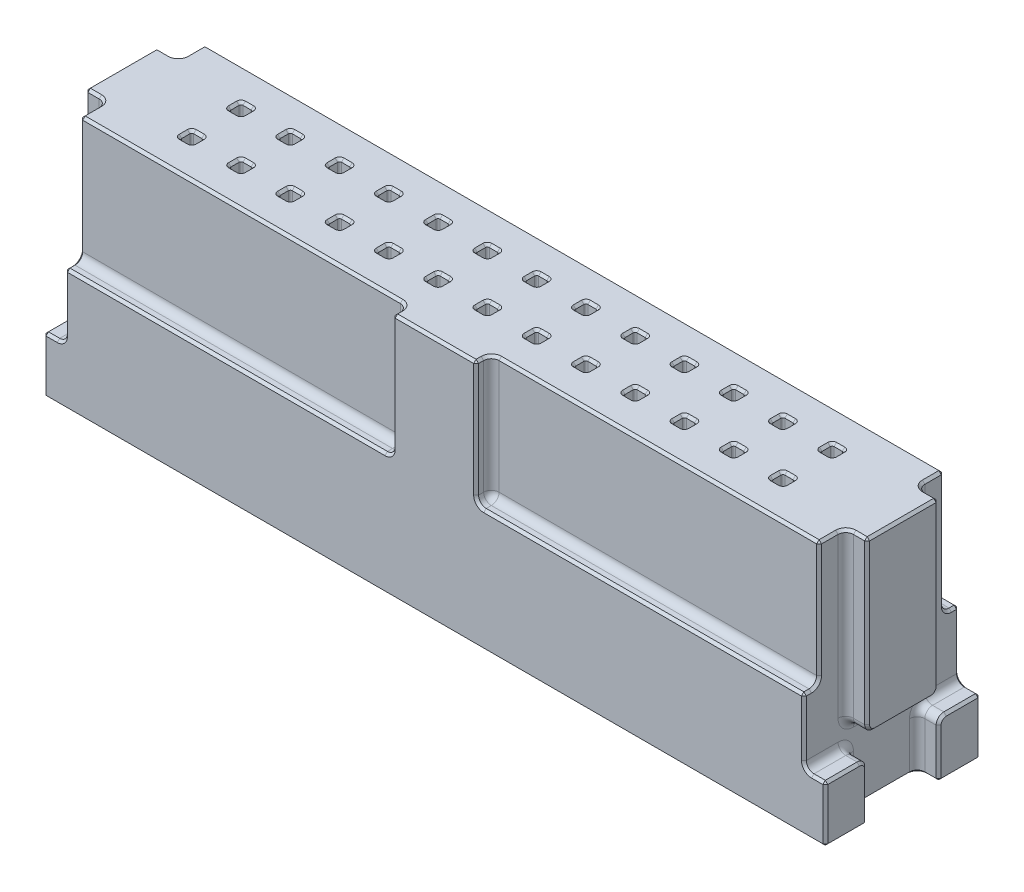
SolidWorks part; units mm, degrees
ref_plane "Front Plane" through (0, 0, 0) normal (0, 0, 1) x (1, 0, 0)
ref_plane "Top Plane" through (0, 0, 0) normal (0, 1, 0) x (1, 0, 0)
ref_plane "Right Plane" through (0, 0, 0) normal (1, 0, 0) x (0, 0, -1)
sketch "Sketch1" plane through (0, 0, 0) normal (0, 1, 0) x (1, 0, 0)
  line L1 (-20.1549, -4.0005) -> (20.1549, -4.0005)
  line L2 (-20.1549, -4.0005) -> (-20.1549, 4.0005)
  line L3 (-20.1549, 4.0005) -> (20.1549, 4.0005)
  line L4 (20.1549, -4.0005) -> (20.1549, 4.0005)
  line L5 (-20.1549, -4.0005) -> (20.1549, 4.0005) construction
  line L6 (-20.1549, 4.0005) -> (20.1549, -4.0005) construction
  point P0 (0, 0)
  dimension "D1" = 40.3098
  dimension "D2" = 8.001
extrude "Boss-Extrude1" add sketch "Sketch1" along normal blind 12.7 contours L3 L4 L1 L2
sketch "Sketch2" plane through (0, 12.7, 0) normal (0, 1, 0) x (1, 0, 0)
  line L1 (-20.1549, 4.0005) -> (-19.05, 4.0005)
  line L2 (-20.1549, 4.0005) -> (-20.1549, 1.8415)
  line L3 (-20.1549, 1.8415) -> (-19.05, 1.8415)
  line L4 (-19.05, 4.0005) -> (-19.05, 1.8415)
  line L5 (-20.1549, -4.0005) -> (-19.05, -4.0005)
  line L6 (-20.1549, -4.0005) -> (-20.1549, -1.8415)
  line L7 (-20.1549, -1.8415) -> (-19.05, -1.8415)
  line L8 (-19.05, -4.0005) -> (-19.05, -1.8415)
  line L9 (20.1549, 4.0005) -> (19.05, 4.0005)
  line L10 (20.1549, 4.0005) -> (20.1549, 1.8415)
  line L11 (20.1549, 1.8415) -> (19.05, 1.8415)
  line L12 (19.05, 4.0005) -> (19.05, 1.8415)
  line L13 (20.1549, -4.0005) -> (19.05, -4.0005)
  line L14 (20.1549, -4.0005) -> (20.1549, -1.8415)
  line L15 (20.1549, -1.8415) -> (19.05, -1.8415)
  line L16 (19.05, -4.0005) -> (19.05, -1.8415)
  dimension "D1" = 1.1049
  dimension "D2" = 2.159
extrude "Cut-Extrude1" cut sketch "Sketch2" against normal blind 9.7993
sketch "Sketch4" plane through (0, 12.7, 0) normal (0, 1, 0) x (1, 0, 0)
  line L1 (-20.1549, -1.8415) -> (-19.05, -1.8415)
  line L2 (-20.1549, -1.8415) -> (-20.1549, 1.8415)
  line L3 (-20.1549, 1.8415) -> (-19.05, 1.8415)
  line L4 (-19.05, -1.8415) -> (-19.05, 1.8415)
  line L5 (20.1549, -1.8415) -> (19.05, -1.8415)
  line L6 (20.1549, -1.8415) -> (20.1549, 1.8415)
  line L7 (20.1549, 1.8415) -> (19.05, 1.8415)
  line L8 (19.05, -1.8415) -> (19.05, 1.8415)
extrude "Cut-Extrude2" cut sketch "Sketch4" against normal up to next from offset 8.7312 offset against normal yes
sketch "Sketch5" plane through (0, 12.7, 0) normal (0, 1, 0) x (1, 0, 0)
  line L0 (19.05, -1.8415) -> (19.05, -4.0005) construction
  line L1 (-19.05, -4.0005) -> (-2.1501, -4.0005)
  line L2 (-19.05, -4.0005) -> (-19.05, -3.2144)
  line L3 (-19.05, -3.2144) -> (-2.1501, -3.2144)
  line L4 (19.05, -4.0005) -> (19.05, -3.2144)
  line L5 (19.05, 4.0005) -> (19.05, 1.8415) construction
  line L6 (-19.05, 4.0005) -> (19.05, 4.0005)
  line L7 (-19.05, 4.0005) -> (-19.05, 3.2144)
  line L8 (-19.05, 3.2144) -> (19.05, 3.2144)
  line L9 (19.05, 4.0005) -> (19.05, 3.2144)
  line L10 (0, -3.2144) -> (0, 3.2144) construction
  line L11 (-2.1501, -3.2144) -> (-2.1501, -4.0005)
  line L12 (2.1501, -3.2144) -> (2.1501, -4.0005)
  line L13 (2.1501, -3.6074) -> (-2.1501, -3.6074) construction
  line L14 (0, -3.6074) -> (0, -3.2144) construction
  line L15 (2.1501, -3.2144) -> (19.05, -3.2144)
  line L16 (2.1501, -4.0005) -> (19.05, -4.0005)
  dimension "D1" = 6.4287
  dimension "D2" = 4.3002
extrude "Cut-Extrude3" cut sketch "Sketch5" against normal blind 6.4008 contours L8 L9 L6 L7
sketch "Sketch6" plane through (0, 12.7, 0) normal (0, 1, 0) x (1, 0, 0)
  line L0 (-20.1549, -1.8415) -> (-20.1549, 1.8415) construction
  line L1 (-15.5499, 0.9601) -> (-14.9301, 0.9601)
  line L2 (-15.5499, 0.9601) -> (-15.5499, 1.5799)
  line L3 (-15.5499, 1.5799) -> (-14.9301, 1.5799)
  line L4 (-14.9301, 0.9601) -> (-14.9301, 1.5799)
  line L5 (-15.5499, 0.9601) -> (-14.9301, 1.5799) construction
  line L6 (-15.5499, 1.5799) -> (-14.9301, 0.9601) construction
  line L7 (19.05, 4.0005) -> (-19.05, 4.0005) construction
  point P0 (-15.24, 1.27)
  dimension "D1" = 0.6198
  dimension "D2" = 4.605
  dimension "D3" = 2.4206
extrude "Cut-Extrude4" cut sketch "Sketch6" against normal blind 6.1011 contours L1 L4 L3 L2
pattern_linear "LPattern1" count 13 spacing 2.54 along (1, 0, 0) count 2 spacing 2.54 along (0, 0, 1) of "Cut-Extrude4"
fillet "Fillet1" radius 0.3969 29 edges at (19.05, 8.3344, -1.8415) (19.05, 8.3344, 1.8415) (-19.05, 8.3344, 1.8415) (-19.05, 8.3344, -1.8415) (0, 6.2992, -3.2144) (-10.6001, 6.2992, 3.2144) (-2.1501, 6.2992, 3.6074) (-2.1501, 9.4996, 3.2144) (2.1501, 6.2992, 3.6074) (10.6001, 6.2992, 3.2144) (2.1501, 9.4996, 3.2144) (-19.05, 3.9688, 0) (19.05, 3.9688, 0) (-19.6025, 3.9688, 1.8415) (-19.6025, 3.9688, -1.8415) (-19.6025, 2.9007, -1.8415) (-19.6025, 2.9007, 1.8415) (19.6024, 3.9688, 1.8415) (19.6024, 3.9688, -1.8415) (19.6024, 2.9007, 1.8415) (19.6024, 2.9007, -1.8415) (19.05, 1.4503, -1.8415) (19.05, 2.9007, -2.921) (19.05, 1.4503, 1.8415) (19.05, 2.9007, 2.921) (-19.05, 2.9007, 2.921) (-19.05, 1.4503, 1.8415) (-19.05, 1.4503, -1.8415) (-19.05, 2.9007, -2.921)
fillet "Fillet3" radius 0.0992 44 edges at (14.9301, 9.6495, 0.9601) (13.0099, 9.6495, 0.9601) (7.3101, 9.6495, 0.9601) (5.3899, 9.6495, 1.5799) (2.8499, 9.6495, 0.9601) (0.3099, 9.6495, 1.5799) (0.3099, 9.6495, 0.9601) (-2.2301, 9.6495, 1.5799) (-2.2301, 9.6495, 0.9601) (-5.3899, 9.6495, 1.5799) (-5.3899, 9.6495, 0.9601) (-10.4699, 9.6495, 1.5799) (-13.0099, 9.6495, 1.5799) (10.4699, 9.6495, -0.9601) (10.4699, 9.6495, -1.5799) (9.8501, 9.6495, -1.5799) (7.3101, 9.6495, -1.5799) (0.3099, 9.6495, -0.9601) (-2.8499, 9.6495, -1.5799) (-4.7701, 9.6495, -0.9601) (-7.9299, 9.6495, -0.9601) (-9.8501, 9.6495, -0.9601) (-9.8501, 9.6495, -1.5799) (-13.0099, 9.6495, -0.9601) (-12.3901, 9.6495, -0.9601) (5.08, 6.5989, -1.5799) (5.08, 6.5989, -0.9601) (7.62, 6.5989, -1.5799) (-10.16, 6.5989, 1.5799) (0.3099, 6.5989, 1.27) (0, 6.5989, 1.5799) (2.54, 6.5989, 0.9601) (2.8499, 6.5989, 1.27) (5.08, 6.5989, 1.5799) (7.3101, 6.5989, 1.27) (7.62, 6.5989, 0.9601) (13.0099, 6.5989, 1.27) (-2.2301, 6.5989, -1.27) (-4.7701, 6.5989, -1.27) (-5.08, 6.5989, -1.5799) (-7.62, 6.5989, -1.5799) (-10.16, 6.5989, -0.9601) (-9.8501, 6.5989, -1.27) (-12.3901, 6.5989, -1.27)
chamfer "Chamfer1" distance 0.127 angle 45 303 edges at (15.5208, 12.7, 1.5508) (15.5499, 12.7, 1.27) (15.5208, 12.7, 0.9892) (15.24, 12.7, 0.9601) (14.9592, 12.7, 0.9892) (14.9301, 12.7, 1.27) (14.9592, 12.7, 1.5508) (15.24, 12.7, 1.5799) (12.9808, 12.7, 1.5508) (13.0099, 12.7, 1.27) (12.9808, 12.7, 0.9892) (12.7, 12.7, 0.9601) (12.4192, 12.7, 0.9892) (12.3901, 12.7, 1.27) (12.4192, 12.7, 1.5508) (12.7, 12.7, 1.5799) (10.4408, 12.7, 1.5508) (10.4699, 12.7, 1.27) (10.4408, 12.7, 0.9892) (10.16, 12.7, 0.9601) (9.8792, 12.7, 0.9892) (9.8501, 12.7, 1.27) (9.8792, 12.7, 1.5508) (10.16, 12.7, 1.5799) (7.9008, 12.7, 1.5508) (7.9299, 12.7, 1.27) (7.9008, 12.7, 0.9892) (7.62, 12.7, 0.9601) (7.3392, 12.7, 0.9892) (7.3101, 12.7, 1.27) (7.3392, 12.7, 1.5508) (7.62, 12.7, 1.5799) (5.3608, 12.7, 1.5508) (5.3899, 12.7, 1.27) (5.3608, 12.7, 0.9892) (5.08, 12.7, 0.9601) (4.7992, 12.7, 0.9892) (4.7701, 12.7, 1.27) (4.7992, 12.7, 1.5508) (5.08, 12.7, 1.5799) (2.8208, 12.7, 1.5508) (2.8499, 12.7, 1.27) (2.8208, 12.7, 0.9892) (2.54, 12.7, 0.9601) (2.2592, 12.7, 0.9892) (2.2301, 12.7, 1.27) (2.2592, 12.7, 1.5508) (2.54, 12.7, 1.5799) (0.2808, 12.7, 1.5508) (0.3099, 12.7, 1.27) (0.2808, 12.7, 0.9892) (0, 12.7, 0.9601) (-0.2808, 12.7, 0.9892) (-0.3099, 12.7, 1.27) (-0.2808, 12.7, 1.5508) (0, 12.7, 1.5799) (-2.2592, 12.7, 1.5508) (-2.2301, 12.7, 1.27) (-2.2592, 12.7, 0.9892) (-2.54, 12.7, 0.9601) (-2.8208, 12.7, 0.9892) (-2.8499, 12.7, 1.27) (-2.8208, 12.7, 1.5508) (-2.54, 12.7, 1.5799) (-4.7992, 12.7, 1.5508) (-4.7701, 12.7, 1.27) (-4.7992, 12.7, 0.9892) (-5.08, 12.7, 0.9601) (-5.3608, 12.7, 0.9892) (-5.3899, 12.7, 1.27) (-5.3608, 12.7, 1.5508) (-5.08, 12.7, 1.5799) (-7.3392, 12.7, 1.5508) (-7.3101, 12.7, 1.27) (-7.3392, 12.7, 0.9892) (-7.62, 12.7, 0.9601) (-7.9008, 12.7, 0.9892) (-7.9299, 12.7, 1.27) (-7.9008, 12.7, 1.5508) (-7.62, 12.7, 1.5799) (-9.8792, 12.7, 1.5508) (-9.8501, 12.7, 1.27) (-9.8792, 12.7, 0.9892) (-10.16, 12.7, 0.9601) (-10.4408, 12.7, 0.9892) (-10.4699, 12.7, 1.27) (-10.4408, 12.7, 1.5508) (-10.16, 12.7, 1.5799) (-12.4192, 12.7, 1.5508) (-12.3901, 12.7, 1.27) (-12.4192, 12.7, 0.9892) (-12.7, 12.7, 0.9601) (-12.9808, 12.7, 0.9892) (-13.0099, 12.7, 1.27) (-12.9808, 12.7, 1.5508) (-12.7, 12.7, 1.5799) (-14.9592, 12.7, 1.5508) (-14.9301, 12.7, 1.27) (-14.9592, 12.7, 0.9892) (-15.24, 12.7, 0.9601) (-15.5208, 12.7, 0.9892) (-15.5499, 12.7, 1.27) (-15.5208, 12.7, 1.5508) (-15.24, 12.7, 1.5799) (15.5208, 12.7, -0.9892) (15.5499, 12.7, -1.27) (15.5208, 12.7, -1.5508) (15.24, 12.7, -1.5799) (14.9592, 12.7, -1.5508) (14.9301, 12.7, -1.27) (14.9592, 12.7, -0.9892) (15.24, 12.7, -0.9601) (12.9808, 12.7, -0.9892) (13.0099, 12.7, -1.27) (12.9808, 12.7, -1.5508) (12.7, 12.7, -1.5799) (12.4192, 12.7, -1.5508) (12.3901, 12.7, -1.27) (12.4192, 12.7, -0.9892) (12.7, 12.7, -0.9601) (10.4408, 12.7, -0.9892) (10.4699, 12.7, -1.27) (10.4408, 12.7, -1.5508) (10.16, 12.7, -1.5799) (9.8792, 12.7, -1.5508) (9.8501, 12.7, -1.27) (9.8792, 12.7, -0.9892) (10.16, 12.7, -0.9601) (7.9008, 12.7, -0.9892) (7.9299, 12.7, -1.27) (7.9008, 12.7, -1.5508) (7.62, 12.7, -1.5799) (7.3392, 12.7, -1.5508) (7.3101, 12.7, -1.27) (7.3392, 12.7, -0.9892) (7.62, 12.7, -0.9601) (5.3608, 12.7, -0.9892) (5.3899, 12.7, -1.27) (5.3608, 12.7, -1.5508) (5.08, 12.7, -1.5799) (4.7992, 12.7, -1.5508) (4.7701, 12.7, -1.27) (4.7992, 12.7, -0.9892) (5.08, 12.7, -0.9601) (2.8208, 12.7, -0.9892) (2.8499, 12.7, -1.27) (2.8208, 12.7, -1.5508) (2.54, 12.7, -1.5799) (2.2592, 12.7, -1.5508) (2.2301, 12.7, -1.27) (2.2592, 12.7, -0.9892) (2.54, 12.7, -0.9601) (0.2808, 12.7, -0.9892) (0.3099, 12.7, -1.27) (0.2808, 12.7, -1.5508) (0, 12.7, -1.5799) (-0.2808, 12.7, -1.5508) (-0.3099, 12.7, -1.27) (-0.2808, 12.7, -0.9892) (0, 12.7, -0.9601) (-2.2592, 12.7, -0.9892) (-2.2301, 12.7, -1.27) (-2.2592, 12.7, -1.5508) (-2.54, 12.7, -1.5799) (-2.8208, 12.7, -1.5508) (-2.8499, 12.7, -1.27) (-2.8208, 12.7, -0.9892) (-2.54, 12.7, -0.9601) (-4.7992, 12.7, -0.9892) (-4.7701, 12.7, -1.27) (-4.7992, 12.7, -1.5508) (-5.08, 12.7, -1.5799) (-5.3608, 12.7, -1.5508) (-5.3899, 12.7, -1.27) (-5.3608, 12.7, -0.9892) (-5.08, 12.7, -0.9601) (-7.3392, 12.7, -0.9892) (-7.3101, 12.7, -1.27) (-7.3392, 12.7, -1.5508) (-7.62, 12.7, -1.5799) (-7.9008, 12.7, -1.5508) (-7.9299, 12.7, -1.27) (-7.9008, 12.7, -0.9892) (-7.62, 12.7, -0.9601) (-9.8792, 12.7, -0.9892) (-9.8501, 12.7, -1.27) (-9.8792, 12.7, -1.5508) (-10.16, 12.7, -1.5799) (-10.4408, 12.7, -1.5508) (-10.4699, 12.7, -1.27) (-10.4408, 12.7, -0.9892) (-10.16, 12.7, -0.9601) (-12.4192, 12.7, -0.9892) (-12.3901, 12.7, -1.27) (-12.4192, 12.7, -1.5508) (-12.7, 12.7, -1.5799) (-12.9808, 12.7, -1.5508) (-13.0099, 12.7, -1.27) (-12.9808, 12.7, -0.9892) (-12.7, 12.7, -0.9601) (-19.05, 6.2992, -3.8059) (19.05, 6.2992, -3.8059) (-19.05, 6.2992, 3.8059) (19.05, 6.2992, 3.8059) (-19.05, 6.4154, -3.3306) (19.05, 6.4154, -3.3306) (-19.05, 6.4154, 3.3306) (19.05, 6.4154, 3.3306) (-19.1662, 0, 1.7253) (-19.8009, 0, 1.8415) (-19.05, 0, 0) (-19.1662, 0, -1.7253) (-19.8009, 0, -1.8415) (20.1549, 0, -2.921) (-20.1549, 0, -2.921) (-20.1549, 1.2519, -1.8415) (-20.1549, 2.7844, -1.9577) (-20.1549, 2.9007, -3.1194) (-20.1549, 1.4503, -4.0005) (0, 0, -4.0005) (20.1549, 1.4503, -4.0005) (-19.8009, 2.9007, -4.0005) (-19.1662, 3.0169, -4.0005) (-19.05, 4.7984, -4.0005) (0, 6.2992, -4.0005) (19.05, 4.7984, -4.0005) (19.1662, 3.0169, -4.0005) (19.8009, 2.9007, -4.0005) (20.1549, 2.9007, -3.1194) (20.1549, 2.7844, -1.9577) (20.1549, 1.2519, -1.8415) (19.8009, 0, -1.8415) (19.1662, 0, -1.7253) (19.05, 0, 0) (19.1662, 0, 1.7253) (19.8009, 0, 1.8415) (-19.05, 9.698, -3.2144) (19.05, 9.698, -3.2144) (-19.05, 9.698, 3.2144) (20.1549, 0, 2.921) (20.1549, 1.2519, 1.8415) (20.1549, 2.7844, 1.9577) (20.1549, 2.9007, 3.1194) (19.05, 9.698, 3.2144) (-20.1549, 0, 2.921) (-20.1549, 1.2519, 1.8415) (-20.1549, 2.7844, 1.9577) (-20.1549, 2.9007, 3.1194) (20.1549, 8.5328, -1.8415) (20.1549, 4.085, -1.7253) (20.1549, 3.9688, 0) (20.1549, 4.085, 1.7253) (20.1549, 8.5328, 1.8415) (19.05, 4.7984, 4.0005) (19.1662, 3.0169, 4.0005) (19.8009, 2.9007, 4.0005) (20.1549, 1.4503, 4.0005) (0, 0, 4.0005) (-20.1549, 1.4503, 4.0005) (-19.8009, 2.9007, 4.0005) (-19.1662, 3.0169, 4.0005) (-19.05, 4.7984, 4.0005) (-10.7985, 6.2992, 4.0005) (-2.2664, 6.4154, 4.0005) (-2.1501, 9.698, 4.0005) (10.7985, 6.2992, 4.0005) (2.2664, 6.4154, 4.0005) (2.1501, 9.698, 4.0005) (-20.1549, 4.085, -1.7253) (-20.1549, 8.5328, -1.8415) (-20.1549, 3.9688, 0) (-20.1549, 4.085, 1.7253) (-20.1549, 8.5328, 1.8415) (19.1662, 12.7, -1.9577) (19.8009, 12.7, -1.8415) (20.1549, 12.7, 0) (19.8009, 12.7, 1.8415) (19.1662, 12.7, 1.9577) (19.05, 12.7, 2.7264) (10.7985, 12.7, 3.2144) (2.2664, 12.7, 3.3306) (2.1501, 12.7, 3.8059) (0, 12.7, 4.0005) (-2.1501, 12.7, 3.8059) (-2.2664, 12.7, 3.3306) (-10.7985, 12.7, 3.2144) (-19.05, 12.7, 2.7264) (-19.1662, 12.7, 1.9577) (-19.8009, 12.7, 1.8415) (-20.1549, 12.7, 0) (-19.8009, 12.7, -1.8415) (-19.1662, 12.7, -1.9577) (-19.05, 12.7, -2.7264) (0, 12.7, -3.2144) (19.05, 12.7, -2.7264) (-14.9592, 12.7, -0.9892) (-14.9301, 12.7, -1.27) (-14.9592, 12.7, -1.5508) (-15.24, 12.7, -1.5799) (-15.5208, 12.7, -1.5508) (-15.5499, 12.7, -1.27) (-15.5208, 12.7, -0.9892) (-15.24, 12.7, -0.9601)
